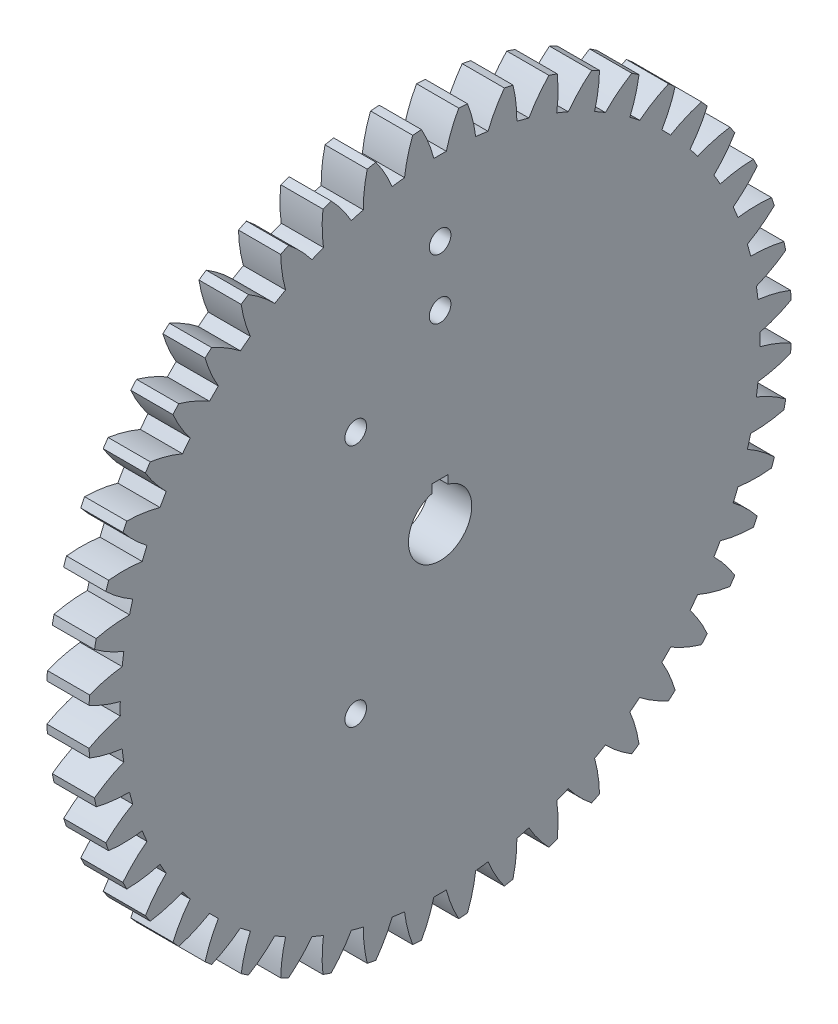
SolidWorks part; units mm, degrees
ref_plane "Plane1" through (0, 0, 0) normal (0, 0, 1) x (1, 0, 0)
ref_plane "Plane2" through (0, 0, 0) normal (0, 1, 0) x (1, 0, 0)
ref_plane "Plane3" through (0, 0, 0) normal (1, 0, 0) x (0, 0, -1)
other "Configuration Table"
sketch "HoldingSke" plane through (0, 0, 0) normal (0, 1, 0) x (1, 0, 0)
  line L0 (0, 0) -> (101.9755, -113.2553)
  line L1 (-15, 0) -> (100, 0) construction
  line L2 (0, 0) -> (-2.1039, 2.3779)
  line L3 (0, 0) -> (-11.863, 4.5341)
  line L4 (0, 0) -> (5.7786, 6.4178)
  line L5 (0, 0) -> (-47.5972, -17.7524)
  line L6 (0, 0) -> (-10.5278, -7.1032)
  line L7 (-2.1039, 2.3779) -> (8.8308, 51.9871)
  line L8 (-76.2, 54.61) -> (-54.9402, 54.61)
  line L9 (-71.009, 38.7566) -> (-53.1078, 45.2721)
  line L10 (-76.2, 71.12) -> (104.1128, 71.12)
  line L11 (0, 0) -> (-12.7, 0)
  line L12 (-76.2, 101.6) -> (-76.0298, 101.6)
  line L13 (24.9733, 27.94) -> (52.9518, 28.4284)
  line L14 (24.9733, 27.94) -> (24.9746, 27.94)
  line L15 (24.9733, 27.94) -> (100.4006, 29.5858)
  circle A0 centre (0, 0) radius 9.525
  circle A1 centre (0, 0) radius 38.1
  circle A2 centre (0, 0) radius 38.1
  circle A3 centre (0, 0) radius 9.525
  dimension "Num_teeth" = 48
  dimension "H" = 19.05
  dimension "Pitch_radius" = 180.3128
  dimension "Width" = 12.7
  dimension "Thickness" = 12.7
sketch "BasProSke" plane through (0, 0, 0) normal (0, 1, 0) x (1, 0, 0)
  line L0 (-10, 0) -> (60, 0) construction
  line L1 (0, 0) -> (0, 105.8333)
  line L2 (0, 0) -> (12.7, 0)
  line L3 (12.7, 0) -> (12.7, 105.8333)
  line L4 (12.7, 105.8333) -> (0, 105.8333)
  dimension "Thickness" = 12.7
  dimension "Diameter" = 211.6667
revolve "Base-Revolve" add sketch "BasProSke" angle 360 about L0
sketch "TooCutSke" plane through (0, 0, 0) normal (1, 0, 0) x (0, 0, -1)
  line L1 (0, 0) -> (0, 107) construction
  line L2 (0, 0) -> (-3.622, 101.5354) construction
  line L3 (0, 0) -> (-13.284, 202.675) construction
  line L4 (-3.622, 101.5354) -> (-6.642, 101.3375) construction
  arc A0 (1.8768, 96.2888) -> (-1.8768, 96.2888) centre (0, 0) ccw
  arc A1 (5.6186, 105.7095) -> (-5.6186, 105.7095) centre (0, 0) ccw
  circle A2 centre (0, 0) radius 101.6 construction
  circle A3 centre (0, 0) radius 95.4728 construction
  arc A4 (-1.8768, 96.2888) -> (-5.6186, 105.7095) centre (-41.2227, 86.1147) ccw
  arc A5 (5.6186, 105.7095) -> (1.8768, 96.2888) centre (41.2227, 86.1147) ccw
extrude "ToothCut" cut sketch "TooCutSke" along normal through all
fillet "Breaks" [suppressed] radius 0.0847 tangent propagation no
fillet "RootFillets" [suppressed] radius 1.0596
pattern_circular "TeethCuts" count 48 every 7.5 about axis through (-10, 0, 0) along (1, 0, 0) of "ToothCut", "RootFillets", "Breaks"
sketch "HubNeaOneSke" plane through (0, 0, 0) normal (-1, 0, 0) x (0, 0, 1)
  circle A0 centre (0, 0) radius 38.1
  dimension "Diameter" = 76.2
extrude "HubNearOne" [suppressed] add sketch "HubNeaOneSke" along normal blind 38.1001
sketch "HubNeaBotSke" plane through (0, 0, 0) normal (-1, 0, 0) x (0, 0, 1)
  circle A0 centre (0, 0) radius 38.1
  dimension "Diameter" = 76.2
extrude "HubNearBoth" [suppressed] add sketch "HubNeaBotSke" along normal blind 19.05
ref_plane "FarPln" through (12.7, 0, 0) normal (1, 0, 0) x (0, 0, -1)
sketch "HubFarSke" plane through (12.7, 0, 0) normal (1, 0, 0) x (0, 0, -1)
  circle A0 centre (0, 0) radius 38.1
  dimension "Diameter" = 76.2
extrude "HubFar" [suppressed] add sketch "HubFarSke" along normal blind 19.05
sketch "BorSke" plane through (0, 0, 0) normal (1, 0, 0) x (0, 0, -1)
  circle A0 centre (0, 0) radius 9.525
  dimension "Diameter" = 19.05
extrude "Bore" cut sketch "BorSke" along normal mid plane 101.6001
sketch "KeySke" plane through (0, 0, 0) normal (1, 0, 0) x (0, 0, -1)
  line L0 (-2.3813, 0) -> (-2.3813, 11.7348)
  line L1 (-2.3813, 11.7348) -> (2.3813, 11.7348)
  line L2 (2.3813, 11.7348) -> (2.3813, 0)
  line L3 (0, 0) -> (0, 34) construction
  line L4 (-2.3813, 0) -> (2.3813, 0)
  dimension "Width" = 4.7625
extrude "Keyway" cut sketch "KeySke" along normal mid plane 101.6001
pattern_circular "Keyway2" [suppressed] count 2 every 90 about axis through (-10, 0, 0) along (1, 0, 0)
sketch "Sketch1" plane through (0, 0, 0) normal (-1, 0, 0) x (0, 0, 1)
  line L0 (-32.7257, 64.77) -> (54.9532, 64.77) construction
  circle A0 centre (0, 73.7743) radius 3.2512
  circle A1 centre (0, 55.7657) radius 3.2512
  dimension "D1" = 6.5024
  dimension "D2" = 18.0086
  dimension "D3" = 64.77
extrude "Cut-Extrude1" cut sketch "Sketch1" against normal through all
sketch "Sketch2" plane through (0, 0, 0) normal (-1, 0, 0) x (0, 0, 1)
  line L0 (41.1124, 0) -> (-29.3128, 0) construction
  circle A0 centre (25.4, -36.703) radius 3.2512
  circle A1 centre (25.4, 36.703) radius 3.2512
  dimension "D2" = 6.5024
  dimension "D1" = 73.406
  dimension "D3" = 25.4
extrude "Cut-Extrude2" cut sketch "Sketch2" against normal through all
equation "' \"Pitch@HoldingSke\" = 4"
equation "' \"Num_teeth@HoldingSke\" = 12"
equation "' \"Ap@HoldingSke\" =  20"
equation "' \"Ap@HoldingSke\" = 20"
equation "' \"Width@HoldingSke\" = 0.5"
equation "' \"Hub_dia@HoldingSke\"= 1"
equation "' \"Hub_dia@HoldingSke\" = 1"
equation "' \"Overall_len@HoldingSke\" = 1.0"
equation "' \"Bore@HoldingSke\" = 0.75"
equation "' \"T_dim@HoldingSke\" = 0.85"
equation "' \"Width@KeySke\" = 0.25"
equation "' \"Show_teeth@HoldingSke\" = 13"
equation "' \"Backlash@HoldingSke\" = 0.009"
equation "' \"Addendum_fac@HoldingSke\" = 1.0"
equation "' \"Dedendum_fac@HoldingSke\" = 1.25"
equation "' \"Dedendum_add@HoldingSke\" = 0.00005"
equation "' \"Clearance_fac@HoldingSke\" = 0.25"
equation "' \"Pitch@HoldingSke\" = 0.5"
equation "' \"Num_teeth@HoldingSke\" = 23"
equation "' \"Show_teeth@HoldingSke\" = 23"
equation "' \"Backlash@HoldingSke\" = 0.0375"
equation "\"Overcut_dia@TooCutSke\" = (\"Num_teeth@HoldingSke\" + 2 * \"Addendum_fac@HoldingSke\") / \"Pitch@HoldingSke\" + 0.002"
equation "\"Pitch_dia@TooCutSke\" = \"Num_teeth@HoldingSke\" / \"Pitch@HoldingSke\""
equation "\"Base_dia@TooCutSke\" = \"Num_teeth@HoldingSke\" / \"Pitch@HoldingSke\" * cos((\"Ap@HoldingSke\"  * 3.14159265 / 180))"
equation "\"Root_dia@TooCutSke\" = (\"Num_teeth@HoldingSke\" + 2) / \"Pitch@HoldingSke\" - 2 * (\"Addendum_fac@HoldingSke\" + \"Dedendum_fac@HoldingSke\") / \"Pitch@HoldingSke\" - \"Dedendum_add@HoldingSke\" * 2"
equation "\"Half_ang@TooCutSke\" = 180 / \"Num_teeth@HoldingSke\""
equation "\"Half_CT@TooCutSke\" = \"Num_teeth@HoldingSke\" / \"Pitch@HoldingSke\" * sin((3.14159265 / 2 / \"Num_teeth@HoldingSke\")) / 2 - 7 * \"Backlash@HoldingSke\" / 4"
equation "\"Flank_rad@TooCutSke\" = \"Num_teeth@HoldingSke\" / \"Pitch@HoldingSke\" / 5"
equation "\"Radius@RootFillets\" = \"Clearance_fac@HoldingSke\" / \"Pitch@HoldingSke\" + \"Dedendum_add@HoldingSke\""
equation "\"Break_rad@Breaks\" = 0.02 / \"Pitch@HoldingSke\""
equation "\"Thickness@HoldingSke\" = \"Width@HoldingSke\""
equation "\"OAL@HoldingSke\" = \"Thickness@HoldingSke\""
equation "\"MHD@HoldingSke\" = (\"Num_teeth@HoldingSke\" + 2) / \"Pitch@HoldingSke\" - 2 * (\"Addendum_fac@HoldingSke\" + \"Dedendum_fac@HoldingSke\")  / \"Pitch@HoldingSke\" - \"Dedendum_add@HoldingSke\" * 2"
equation "\"MBD@HoldingSke\" = (\"Num_teeth@HoldingSke\" + 2) / \"Pitch@HoldingSke\" - 2 * (\"Addendum_fac@HoldingSke\" + \"Dedendum_fac@HoldingSke\")  / \"Pitch@HoldingSke\" - \"Dedendum_add@HoldingSke\" * 2 - 0.002"
equation "\"MHD@HoldingSke\" = ((sgn( \"MHD@HoldingSke\" - \"Hub_dia@HoldingSke\" )-1)*( \"MHD@HoldingSke\" - \"Hub_dia@HoldingSke\" ))/-2+ \"Hub_dia@HoldingSke\""
equation "\"MBD@HoldingSke\" = ((sgn( \"MBD@HoldingSke\" - \"Bore@HoldingSke\" )-1)*( \"MBD@HoldingSke\" - \"Bore@HoldingSke\" ))/-2+ \"Bore@HoldingSke\""
equation "\"OAL@HoldingSke\" = ((sgn( \"OAL@HoldingSke\" - \"Overall_len@HoldingSke\" )+1)*( \"OAL@HoldingSke\" - \"Overall_len@HoldingSke\" ))/2 + \"Overall_len@HoldingSke\" + 0.000002"
equation "\"Num_teeth@TeethCuts\" = int( \"Show_teeth@HoldingSke\" ) + 1"
equation "\"Num_teeth@TeethCuts\" = ((sgn( \"Num_teeth@TeethCuts\" - \"Num_teeth@HoldingSke\" )-1)*( \"Num_teeth@TeethCuts\" - \"Num_teeth@HoldingSke\" ))/-2+ \"Num_teeth@HoldingSke\""
equation "\"Num_teeth@TeethCuts\" = ((sgn( \"Num_teeth@TeethCuts\" - 2.0)+1)*( \"Num_teeth@TeethCuts\" - 2.0))/2 +2.0"
equation "\"Angle@TeethCuts\" = 360.0 / \"Num_teeth@HoldingSke\""
equation "\"Diameter@BasProSke\" = (\"Num_teeth@HoldingSke\" + 2 * \"Addendum_fac@HoldingSke\") / \"Pitch@HoldingSke\""
equation "\"Thickness@BasProSke\"  = \"Thickness@HoldingSke\""
equation "' \"Fillet_rad@BasProSke\" =  \"Thickness@HoldingSke\" * 0.05"
equation "' \"Fillet_rad@BasProSke\" = \"Thickness@HoldingSke\" * 0.05"
equation "\"MHD@HoldingSke\" = ((sgn( \"MHD@HoldingSke\" - \"Root_dia@TooCutSke\" )-1)*( \"MHD@HoldingSke\" - \"Root_dia@TooCutSke\" ))/-2+ \"Root_dia@TooCutSke\""
equation "\"Diameter@HubNeaOneSke\" = \"MHD@HoldingSke\""
equation "\"Length@HubNearOne\" = \"OAL@HoldingSke\" - \"Thickness@BasProSke\""
equation "\"Diameter@HubNeaBotSke\" = \"MHD@HoldingSke\""
equation "\"Length@HubNearBoth\" = ( \"OAL@HoldingSke\" - \"Thickness@BasProSke\" ) / 2.0"
equation "\"Thickness@FarPln\" = \"Thickness@BasProSke\""
equation "\"Diameter@HubFarSke\" = \"MHD@HoldingSke\""
equation "\"Length@HubFar\" = ( \"OAL@HoldingSke\" - \"Thickness@BasProSke\" ) / 2.0"
equation "\"Diameter@BorSke\" = \"MBD@HoldingSke\""
equation "\"D1@Bore\" = \"OAL@HoldingSke\" * 2.0"
equation "\"D1@Keyway\" = \"OAL@HoldingSke\" * 2.0"
equation "\"Offset@KeySke\" = \"T_dim@HoldingSke\" - \"MBD@HoldingSke\" / 2.0"
